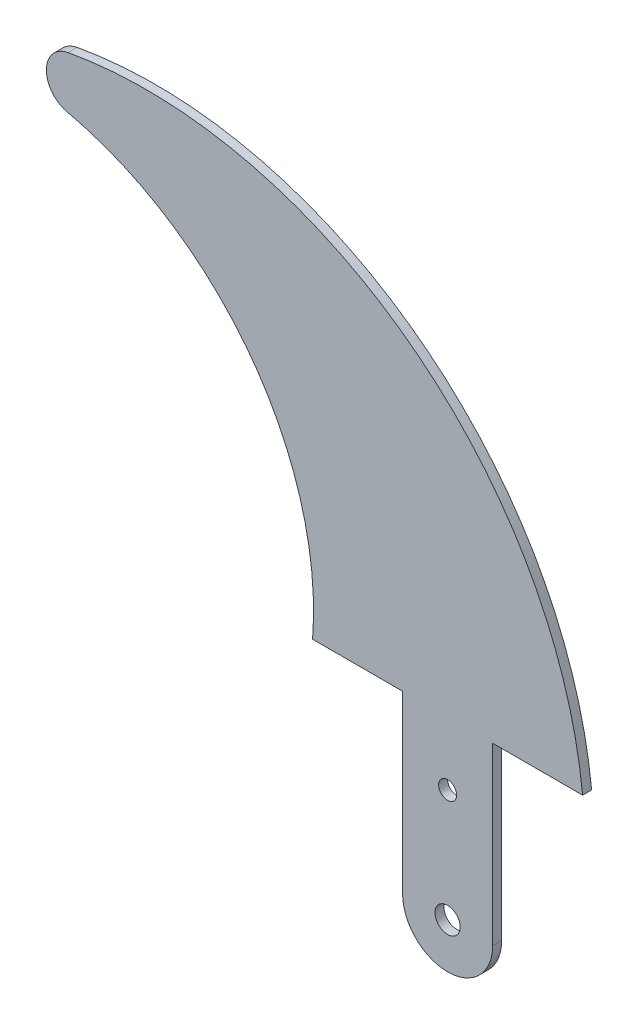
SolidWorks part; units mm, degrees
ref_plane "Alzado" through (0, 0, 0) normal (0, 0, 1) x (1, 0, 0)
ref_plane "Planta" through (0, 0, 0) normal (0, 1, 0) x (1, 0, 0)
ref_plane "Vista lateral" through (0, 0, 0) normal (1, 0, 0) x (0, 0, -1)
sketch "Model" plane through (0, 0, 0) normal (0, 0, 1) x (1, 0, 0)
  line L0 (60.206, 3.7384) -> (50.206, 3.7384)
  line L1 (50.206, 3.7384) -> (50.206, -15.7616)
  line L2 (40.206, -15.7616) -> (40.206, 3.7384)
  line L3 (40.206, 3.7384) -> (30.206, 3.7384)
  circle A0 centre (45.206, -15.7616) radius 1.4
  circle A1 centre (45.206, -3.2616) radius 1
  arc A2 (40.206, -15.7616) -> (50.206, -15.7616) centre (45.206, -15.7616) ccw
  arc A3 (3.0403, 46.6038) -> (2.9116, 40.8534) centre (3.565, 43.7154) ccw
  arc A4 (30.206, 3.7384) -> (2.9116, 40.8534) centre (-4.9324, 6.4912) ccw
  arc A5 (60.206, 3.7384) -> (3.0403, 46.6038) centre (11.748, -1.3345) ccw
base flange "Brida base1" sketch "Model" thickness 1 reverse thickness direction no parameters "D1"=0.7366
sketch "Líneas de pliegue1" [suppressed] plane through (0, 0, 0) normal (0, 1, 0) x (1, 0, 0)
sketch "Cuadro delimitador1" [suppressed] plane through (0, 0, 0) normal (0, 1, 0) x (1, 0, 0)
sheet metal parameters "Chapa metálica1" thickness 1 parameters "D1"=0.7366
flat pattern "Chapa desplegada1" [suppressed]
sketch "Líneas de pliegue2" plane through (0, 0, 0) normal (0, 1, 0) x (1, 0, 0)
sketch3d "Cuadro delimitador2" [suppressed]
  line L0 (17.55, 78.8574, 0) -> (-26.7316, 11.6177, 0) construction
  line L1 (45.7074, 60.3141, 0) -> (1.4258, -6.9257, 0) construction
  line L2 (17.55, 78.8574, 0) -> (45.7074, 60.3141, 0) construction
  line L3 (-26.7316, 11.6177, 0) -> (1.4258, -6.9257, 0) construction
